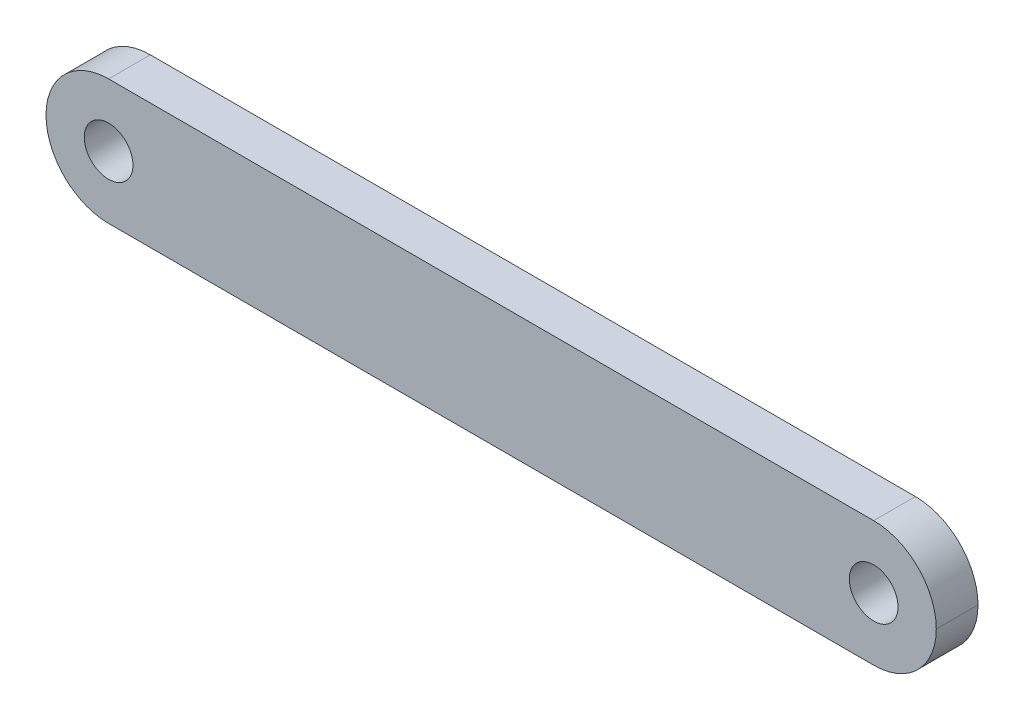
SolidWorks part; units mm, degrees
ref_plane "Front" through (0, 0, 0) normal (0, 0, 1) x (1, 0, 0)
ref_plane "Top" through (0, 0, 0) normal (0, 1, 0) x (1, 0, 0)
ref_plane "Right" through (0, 0, 0) normal (1, 0, 0) x (0, 0, -1)
sketch "Esquisse1" plane through (0, 0, 0) normal (0, 0, 1) x (1, 0, 0)
  line L0 (0, 9) -> (9, 9) construction
  line L1 (0, 0) -> (128, 0)
  line L2 (0, 0) -> (0, 18)
  line L3 (0, 18) -> (128, 18)
  line L4 (128, 0) -> (128, 18)
  line L5 (64, 0) -> (64, 18) construction
  circle A0 centre (9, 9) radius 3.5
  circle A1 centre (119, 9) radius 3.5
  dimension "D2" = 7
  dimension "D4" = 110
  dimension "D1" = 18
  dimension "D3" = 9
extrude "Boss.-Extru.1" add sketch "Esquisse1" along normal blind 6
fillet "Congé1" radius 9 4 edges at (128, 18, 3) (128, 0, 3) (0, 0, 3) (0, 18, 3)
